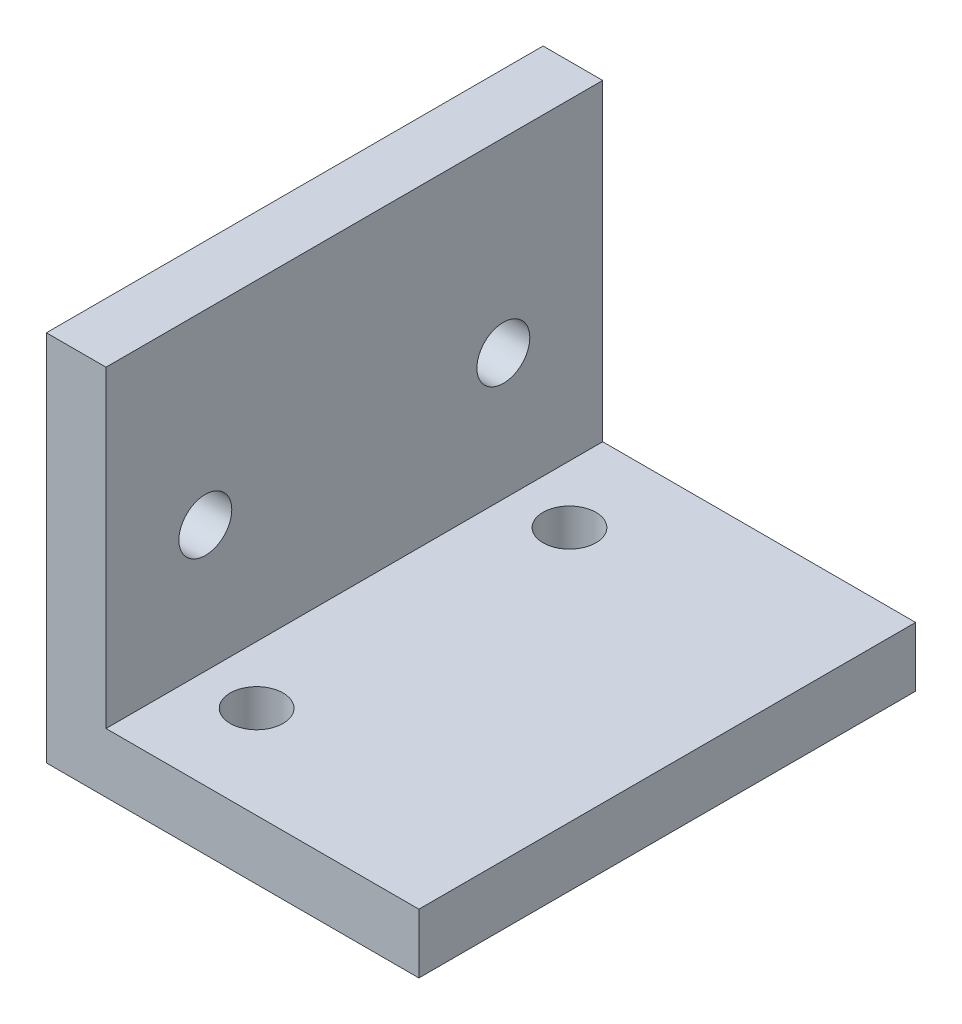
SolidWorks part; units mm, degrees
ref_plane "Front" through (0, 0, 0) normal (0, 0, 1) x (1, 0, 0)
ref_plane "Top" through (0, 0, 0) normal (0, 1, 0) x (1, 0, 0)
ref_plane "Right" through (0, 0, 0) normal (1, 0, 0) x (0, 0, -1)
ref_axis "side-side" through (80.9, 0, 0) along (-1, 0, 0)
ref_axis "up-down" through (0, 50, 0) along (0, -1, 0)
ref_axis "front-back" through (0, 0, -80.9) along (0, 0, 1)
sketch "Sketch1" plane through (0, 0, 0) normal (0, 0, 1) x (1, 0, 0)
  line L1 (0, 0) -> (19.05, 0)
  line L2 (0, 0) -> (0, 19.05)
  line L3 (0, 19.05) -> (3.048, 19.05)
  line L4 (19.05, 0) -> (19.05, 3.048)
  line L7 (19.05, 3.048) -> (3.048, 3.048)
  line L8 (3.048, 19.05) -> (3.048, 3.048)
  dimension "D1" = 19.05
  dimension "D2" = 3.048
extrude "Boss-Extrude1" add sketch "Sketch1" along normal blind 25.4
sketch "Sketch2" plane through (3.048, 0, 0) normal (1, 0, 0) x (0, 0, -1)
  line L0 (-25.4, 19.05) -> (0, 0) construction
  line L1 (-20.32, 9.525) -> (-5.08, 9.525) construction
  line L2 (-25.4, 3.048) -> (-25.4, 19.05) construction
  point P6 (-12.7, 9.525)
  dimension "D1" = 5.08
hole_wizard "#6-32 Tapped Hole1" positions "Sketch4" profile "Sketch3" tap size "#6-32" standard "ANSI Inch" end condition through all
sketch "Sketch4" plane through (3.048, 0, 0) normal (1, 0, 0) x (0, 0, -1)
  point P0 (-20.32, 9.525)
  point P3 (-5.08, 9.525)
sketch "Sketch3" plane through (3.048, 9.525, 20.32) normal (0, 1, 0) x (0, 0, -1)
  line L0 (0, 0) -> (0, 3.048)
  line L1 (0, 3.048) -> (1.3525, 3.048)
  line L2 (1.3525, 3.048) -> (1.3525, 0)
  line L5 (1.3525, 0) -> (0, 0)
  line L11 (0, -6.35) -> (0, 107.95) construction
  dimension "Thread Major Dia." = 2.7051
  dimension "Thru Tap Drill Depth" = 3.048
hole_wizard "#6-32 Tapped Hole2" positions "Sketch6" profile "Sketch5" tap size "#6-32" standard "ANSI Inch" end condition through all
sketch "Sketch6" plane through (0, 3.048, 0) normal (0, 1, 0) x (1, 0, 0)
  point P0 (6, -20.65)
  point P3 (6, -4.65)
sketch "Sketch5" plane through (6, 3.048, 20.65) normal (1, 0, 0) x (0, 0, 1)
  line L0 (0, 0) -> (0, 3.048)
  line L1 (0, 3.048) -> (1.3525, 3.048)
  line L2 (1.3525, 3.048) -> (1.3525, 0)
  line L5 (1.3525, 0) -> (0, 0)
  line L11 (0, -6.35) -> (0, 107.95) construction
  dimension "Thread Major Dia." = 2.7051
  dimension "Thru Tap Drill Depth" = 3.048
